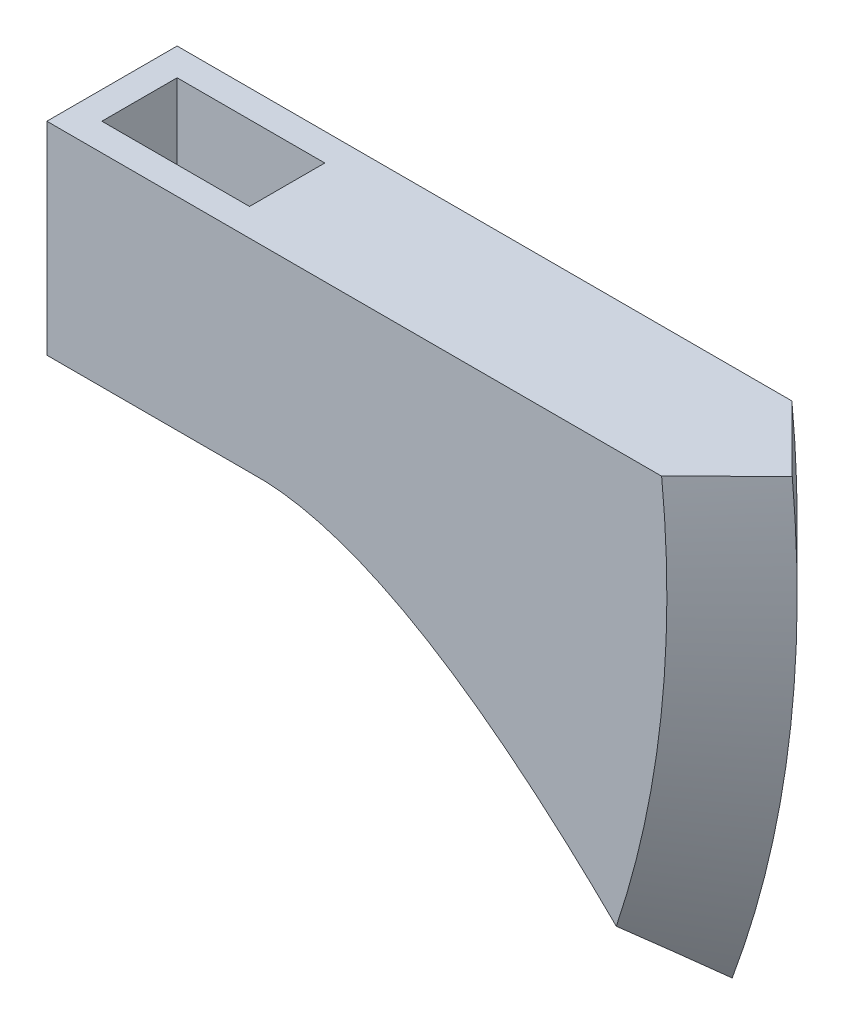
SolidWorks part; units mm, degrees
ref_plane "Front Plane" through (0, 0, 0) normal (0, 0, 1) x (1, 0, 0)
ref_plane "Top Plane" through (0, 0, 0) normal (0, 1, 0) x (1, 0, 0)
ref_plane "Right Plane" through (0, 0, 0) normal (1, 0, 0) x (0, 0, -1)
sketch "Sketch1" plane through (0, 0, 0) normal (0, 0, 1) x (1, 0, 0)
  line L0 (-34.137, -14) -> (-34.137, -28)
  line L1 (-34.137, -14) -> (-20.137, -14)
  line L2 (-34.137, -28) -> (-20.137, -28)
  line L5 (-34.137, -21) -> (-53.6986, -21) construction
  line L6 (-20.137, -28) -> (-8.5775, -27.5828) construction
  line L7 (-8.5775, -27.5828) -> (9.0915, -46.4949) construction
  line L8 (-20.137, -14) -> (13.359, -14)
  arc A0 (13.359, -14) -> (9.0915, -46.4949) centre (-59.19, -21) cw
  spline S1 degree 2 poles (-20.137, -28) (-8.5775, -27.5828) (9.0915, -46.4949) knots 0 0 0 1 1 1
  dimension "D1" = 14
  dimension "D2" = 14
extrude "Boss-Extrude1" add sketch "Sketch1" along normal blind 9
sketch "Sketch2" plane through (0, -14, 0) normal (0, 1, 0) x (1, 0, 0)
  line L0 (13.359, 0) -> (-34.137, 0) construction
  line L1 (-32.237, -1.9) -> (-22.037, -1.9)
  line L2 (-32.237, -1.9) -> (-32.237, -7.1)
  line L3 (-32.237, -7.1) -> (-22.037, -7.1)
  line L4 (-22.037, -1.9) -> (-22.037, -7.1)
  line L5 (13.359, -9) -> (-34.137, -9) construction
  line L6 (-34.137, -9) -> (-34.137, 0) construction
  dimension "D1" = 1.9
  dimension "D2" = 1.9
  dimension "D3" = 5.2
  dimension "D4" = 1.9
  dimension "D5" = 10.2
extrude "Cut-Extrude1" cut sketch "Sketch2" against normal through all both and the other way through all
chamfer "Chamfer1" distance 5 angle 45 2 edges at (13.0754, -30.4904, 0) (13.0754, -30.4904, 9)
